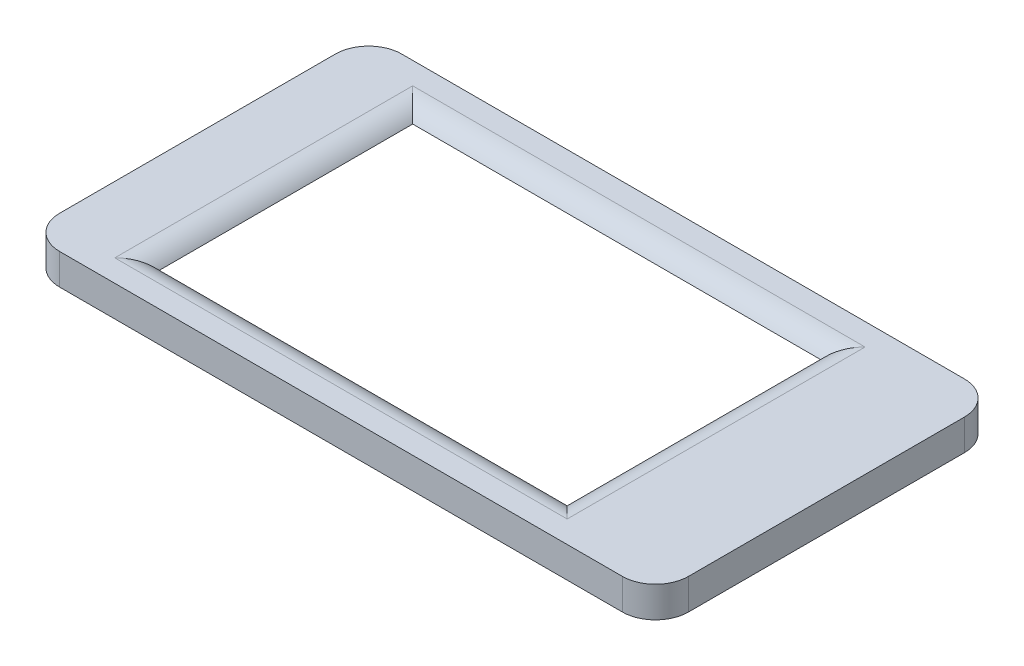
SolidWorks part; units mm, degrees
material "ABS"
ref_plane "Спереди" through (0, 0, 0) normal (0, 0, 1) x (1, 0, 0)
ref_plane "Сверху" through (0, 0, 0) normal (0, 1, 0) x (1, 0, 0)
ref_plane "Справа" through (0, 0, 0) normal (1, 0, 0) x (0, 0, -1)
sketch "Эскиз1" plane through (0, 0, 0) normal (0, 1, 0) x (1, 0, 0)
  line L3 (-59, 31) -> (55, 31)
  line L6 (-59, -31) -> (55, -31)
  line L7 (55, 31) -> (55, -31)
  line L12 (-59, 31) -> (-59, -31)
  point P0 (0, 0)
extrude "Бобышка-Вытянуть1" add sketch "Эскиз1" along normal blind 5.6
sketch "Эскиз5" plane through (0, 0, 0) normal (0, -1, 0) x (1, 0, 0)
  circle A0 centre (-54, 21) radius 3
  circle A1 centre (-54, -21) radius 3
  circle A2 centre (39, 21) radius 3
  circle A3 centre (39, -21) radius 3
extrude "под гайку" cut sketch "Эскиз5" against normal blind 3
sketch "Эскиз7" plane through (0, 0, 0) normal (0, -1, 0) x (1, 0, 0)
  line L6 (35, -29) -> (-50, -29)
  line L7 (35, -29) -> (35, 29)
  line L8 (35, 29) -> (-50, 29)
  line L9 (-50, -29) -> (-50, 29)
extrude "под LCD" cut sketch "Эскиз7" against normal blind 3.6
sketch "Эскиз11" plane through (0, 5.6, 0) normal (0, 1, 0) x (1, 0, 0)
  line L0 (-12.6056, 22.5401) -> (-12.6056, -41.5105) construction
sketch "Эскиз13" plane through (0, 3.6, 0) normal (0, -1, 0) x (1, 0, 0)
  line L4 (31, 23) -> (-43, 23)
  line L5 (31, 23) -> (31, -23)
  line L6 (31, -23) -> (-43, -23)
  line L7 (-43, 23) -> (-43, -23)
extrude "Вырез-Вытянуть1" cut sketch "Эскиз13" against normal blind 10
fillet "Скругление2" radius 5 4 edges at (-43, 5.6, 0) (-6, 5.6, 23) (31, 5.6, 0) (-6, 5.6, -23)
fillet "Скругление3" radius 6 4 edges at (-59, 2.8, 31) (-59, 2.8, -31) (55, 2.8, 31) (55, 2.8, -31)
